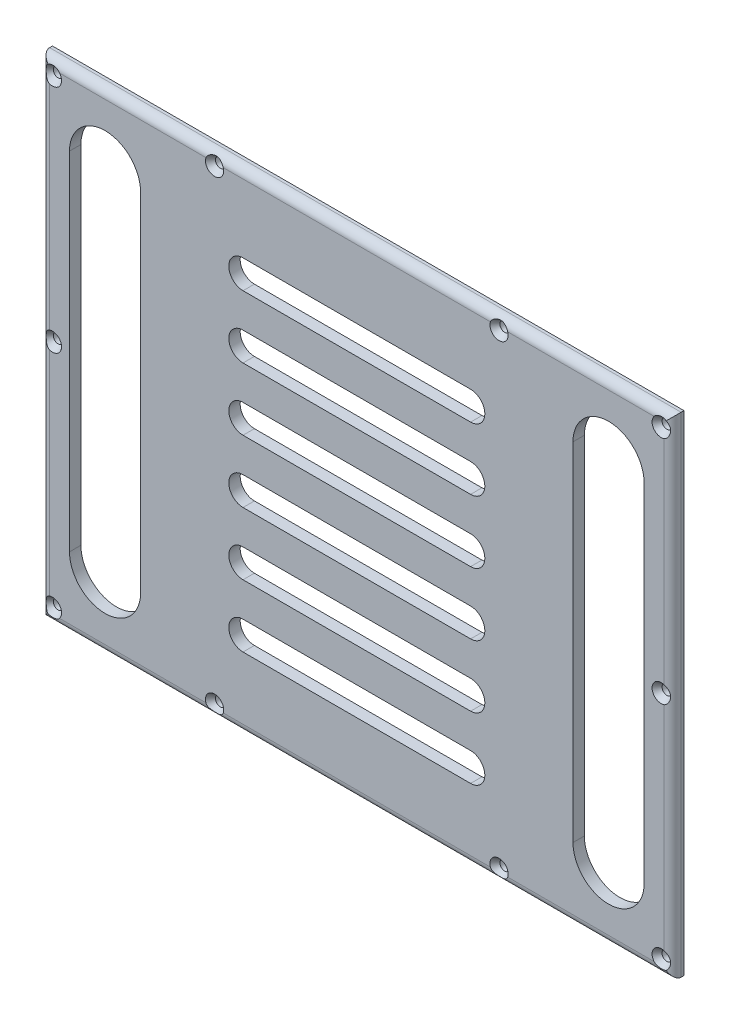
SolidWorks part; units mm, degrees
ref_plane "Front Plane" through (0, 0, 0) normal (1, 0, 0) x (0, 1, 0)
ref_plane "Top Plane" through (0, 0, 0) normal (0, 0, 1) x (0, 1, 0)
ref_plane "Right Plane" through (0, 0, 0) normal (0, 1, 0) x (-1, 0, 0)
sketch "Sketch1" plane through (0, 0, 0) normal (0, 0, 1) x (0, 1, 0)
  line L0 (86, 222) -> (86, 0) construction
  line L1 (0, 0) -> (172, 0)
  line L2 (0, 0) -> (0, 222)
  line L3 (0, 222) -> (172, 222)
  line L4 (172, 0) -> (172, 222)
  line L5 (30, 151) -> (30, 71) construction
  line L14 (35, 151) -> (35, 71)
  line L15 (25, 151) -> (25, 71)
  line L16 (0, 111) -> (191, 111) construction
  line L17 (52, 151) -> (52, 71) construction
  line L18 (57, 151) -> (57, 71)
  line L19 (47, 151) -> (47, 71)
  line L20 (74, 151) -> (74, 71) construction
  line L21 (79, 151) -> (79, 71)
  line L22 (69, 151) -> (69, 71)
  line L23 (96, 151) -> (96, 71) construction
  line L24 (101, 151) -> (101, 71)
  line L25 (91, 151) -> (91, 71)
  line L26 (118, 151) -> (118, 71) construction
  line L27 (123, 151) -> (123, 71)
  line L28 (113, 151) -> (113, 71)
  line L29 (140, 151) -> (140, 71) construction
  line L30 (145, 151) -> (145, 71)
  line L31 (135, 151) -> (135, 71)
  line L32 (25, 199.5) -> (147, 199.5) construction
  line L35 (25, 212) -> (147, 212)
  line L36 (25, 187) -> (147, 187)
  line L37 (25, 22.5) -> (147, 22.5) construction
  line L38 (25, 35) -> (147, 35)
  line L39 (25, 10) -> (147, 10)
  line L98 (162, 151) -> (162, 71) construction
  line L99 (167, 151) -> (167, 71)
  line L100 (157, 151) -> (157, 71)
  line L101 (162, 151) -> (162, 71) construction
  line L102 (167, 151) -> (167, 71)
  line L103 (157, 151) -> (157, 71)
  circle A0 centre (5, 4) radius 1.7
  circle A1 centre (5, 218) radius 1.7
  circle A2 centre (167, 218) radius 1.7
  circle A3 centre (167, 4) radius 1.7
  circle A4 centre (86, 218) radius 1.7
  circle A5 centre (86, 4) radius 1.7
  arc A6 (35, 151) -> (25, 151) centre (30, 151) ccw
  arc A7 (25, 71) -> (35, 71) centre (30, 71) ccw
  arc A8 (57, 151) -> (47, 151) centre (52, 151) ccw
  arc A9 (47, 71) -> (57, 71) centre (52, 71) ccw
  arc A10 (79, 151) -> (69, 151) centre (74, 151) ccw
  arc A11 (69, 71) -> (79, 71) centre (74, 71) ccw
  arc A12 (101, 151) -> (91, 151) centre (96, 151) ccw
  arc A13 (91, 71) -> (101, 71) centre (96, 71) ccw
  arc A14 (123, 151) -> (113, 151) centre (118, 151) ccw
  arc A15 (113, 71) -> (123, 71) centre (118, 71) ccw
  arc A16 (145, 151) -> (135, 151) centre (140, 151) ccw
  arc A17 (135, 71) -> (145, 71) centre (140, 71) ccw
  circle A20 centre (4, 61) radius 1.7
  circle A21 centre (168, 61) radius 1.7
  circle A22 centre (168, 161) radius 1.7
  circle A23 centre (4, 161) radius 1.7
  arc A24 (25, 212) -> (25, 187) centre (25, 199.5) ccw
  arc A25 (147, 187) -> (147, 212) centre (147, 199.5) ccw
  arc A26 (25, 35) -> (25, 10) centre (25, 22.5) ccw
  arc A27 (147, 10) -> (147, 35) centre (147, 22.5) ccw
  arc A68 (167, 151) -> (157, 151) centre (162, 151) ccw
  arc A69 (157, 71) -> (167, 71) centre (162, 71) ccw
  point P20 (162, 76)
  point P21 (86, 199.5)
  point P29 (30, 111)
  point P37 (0, 111)
  point P41 (52, 111)
  point P48 (74, 111)
  point P55 (96, 111)
  point P62 (118, 111)
  point P69 (140, 111)
  point P74 (86, 22.5)
  point P87 (0, 0)
  point P88 (0, 0)
  point P89 (162, 76)
  point P90 (0, 0)
  point P91 (0, 0)
  point P92 (0, 0)
  point P93 (0, 0)
  point P94 (0, 0)
  point P96 (162, 76)
  point P103 (162, 76)
  point P110 (162, 78)
  point P117 (162, 78)
  point P124 (162, 78)
  point P131 (162, 78)
  point P138 (162, 78)
  point P145 (162, 78)
  point P152 (162, 78)
  point P159 (162, 78)
  point P166 (162, 78)
  point P173 (162, 78)
  point P180 (162, 103)
  point P187 (162, 103)
  point P194 (162, 103)
  point P201 (162, 103)
  point P208 (162, 111)
  point P215 (162, 111)
  point P222 (162, 111)
  point P229 (162, 111)
  point P236 (162, 111)
  dimension "D7" = 3.4
  dimension "D1" = 172
  dimension "D2" = 222
  dimension "D3" = 4
  dimension "D4" = 5
  dimension "D5" = 4
  dimension "D6" = 5
  dimension "D13" = 10
  dimension "D14" = 80
  dimension "D16" = 12
  dimension "D8" = 25
  dimension "D9" = 50
  dimension "D10" = 4
  dimension "D11" = 4
  dimension "D12" = 10
  dimension "D17" = 25
  dimension "D15" = 7
extrude "Boss-Extrude2" add sketch "Sketch1" along normal blind 4
chamfer "Chamfer1" distance 1.5 distance2 2 10 edges at (-59.3, 4, 4) (-59.3, 168, 4) (-159.3, 168, 4) (-216.3, 167, 4) (-2.3, 167, 4) (-2.3, 86, 4) (-216.3, 86, 4) (-216.3, 5, 4) (-159.3, 4, 4) (-2.3, 5, 4) first distance on face at (-111, 140, 4)
fillet "Fillet1" radius 3 4 edges at (0, 86, 4) (-222, 86, 4) (-111, 172, 4) (-111, 0, 4)
equation "\"MotorDriverLength\"= 60mm"
equation "\"MotorLength\"= 60"
equation "\"MotorDriverWidth\"=44"
equation "\"MotorWidth\"= 37"
equation "\"InnerWallThickness\"=3"
equation "\"BatteryWidth\"= 60"
equation "\"OuterWallThickness\" = 8"
equation "\"CompartmentHeight\"=37"
equation "\"CompartmentWidth\"= \"MotorDriverLength\""
equation "\"MotorDiameter\"=37"
equation "\"BatteryHeight\"=24.2019"
equation "\"MotorDriverHeight\"=28"
equation "\"CircuitHeight\"=30"
equation "\"FanThickness\"= 10"
equation "\"FanHeight\"=50"
equation "\"MotorShaftHole\"=12"
equation "\"BearingBore\"=4"
equation "\"MinShinWidth\"= 20"
equation "\"ShinThickness\"=10"
equation "\"PivotDistance\"=30"
equation "\"ThighLength\"= 200"
equation "\"KneeLength\" =20"
equation "\"HipBore\"=27"
equation "\"ThighThickness\"=20"
equation "\"MaxBending\"=135"
equation "\"MaxStretchingAngle\"= 140"
equation "\"ThighJointDistance\"=157.485"
equation "\"ShinLength\"=120"
equation "\"BearingDiameter\"= 10"
equation "\"CircuitLength\"=50"
equation "\"ChessisInnerWidth\"= \"OuterWallThickness\" * 2 + \"MotorDriverLength\" + \"MotorDiameter\" + \"InnerWallThickness\" * 3 + \"CircuitLength\""
equation "\"D1@Sketch1\"=\"ChessisInnerWidth\""
equation "\"D2@Sketch1\"=\"ChassisWidth\"+\"OuterWallThickness\"*2"
equation "\"D11@Sketch1\"=\"OuterWallThickness\"/2"
equation "\"D3@Sketch1\"=\"OuterWallThickness\"/2"
equation "\"D5@Sketch1\"=\"OuterWallThickness\"/2"
equation "\"ChessisHeight\"= \"BatteryHeight\" + 10 + \"InnerWallThickness\" + \"MotorDriverHeight\"*2 + 10 + \"OuterWallThickness\" * 2"
equation "\"ChassisWidth\"= \"MotorDriverWidth\"*4+30"
